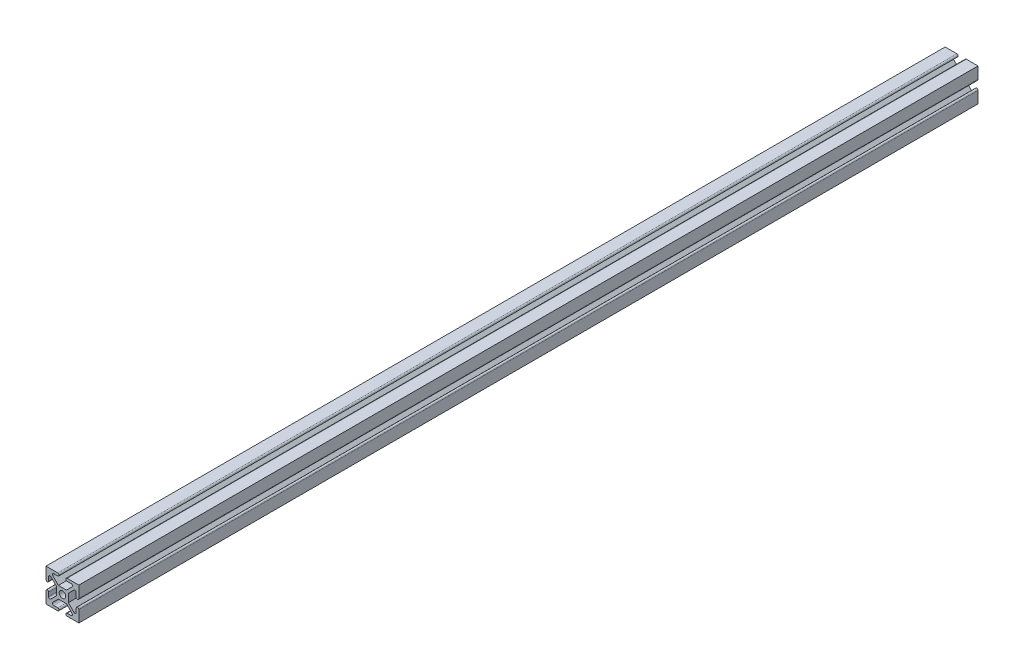
SolidWorks part; units mm, degrees
ref_plane "Front Plane" through (0, 0, 0) normal (0, 0, 1) x (1, 0, 0)
ref_plane "Top Plane" through (0, 0, 0) normal (0, 1, 0) x (1, 0, 0)
ref_plane "Right Plane" through (0, 0, 0) normal (1, 0, 0) x (0, 0, -1)
sketch "Sketch2" plane through (0, 0, 0) normal (0, 0, 1) x (1, 0, 0)
  line L0 (9.4142, 17) -> (5.1716, 21.2426)
  line L5 (9.4142, 17) -> (12.5, 17)
  line L9 (5.8995, 23) -> (8.8995, 23)
  line L10 (8.8995, 25) -> (0, 25)
  line L11 (0, 25) -> (8.8995, 25)
  line L12 (0, 16.1005) -> (0, 25)
  line L13 (2, 19.1005) -> (2, 16.1005)
  line L14 (8, 15.5858) -> (3.7574, 19.8284)
  line L15 (0, 25) -> (35355.3391, -35330.3391) construction
  line L16 (12.5, 12.5) -> (35367.8391, 35367.8391) construction
  line L17 (12.6363, 12.5) -> (50012.6363, 12.5) construction
  line L18 (12.5, 12.3637) -> (12.5, 50012.3637) construction
  line L19 (8, 15.5858) -> (8, 12.5)
  line L20 (9.4142, 8) -> (12.5, 8)
  line L21 (9.4142, 8) -> (5.1716, 3.7574)
  line L22 (5.8995, 2) -> (8.8995, 2)
  line L23 (8.8995, 0) -> (0, 0)
  line L24 (0, 8.8995) -> (0, 0)
  line L25 (2, 5.8995) -> (2, 8.8995)
  line L26 (8, 9.4142) -> (8, 12.5)
  line L27 (8, 9.4142) -> (3.7574, 5.1716)
  line L28 (15.5858, 17) -> (12.5, 17)
  line L29 (15.5858, 17) -> (19.8284, 21.2426)
  line L30 (19.1005, 23) -> (16.1005, 23)
  line L31 (16.1005, 25) -> (25, 25)
  line L32 (25, 16.1005) -> (25, 25)
  line L33 (23, 19.1005) -> (23, 16.1005)
  line L34 (17, 15.5858) -> (21.2426, 19.8284)
  line L35 (17, 15.5858) -> (17, 12.5)
  line L36 (17, 9.4142) -> (17, 12.5)
  line L37 (15.5858, 8) -> (12.5, 8)
  line L38 (17, 9.4142) -> (21.2426, 5.1716)
  line L39 (23, 5.8995) -> (23, 8.8995)
  line L40 (25, 8.8995) -> (25, 0)
  line L41 (16.1005, 0) -> (25, 0)
  line L42 (19.1005, 2) -> (16.1005, 2)
  line L43 (15.5858, 8) -> (19.8284, 3.7574)
  arc A0 (5.1716, 21.2426) -> (5.8995, 23) centre (5.8995, 21.9706) cw
  arc A1 (0, 16.1005) -> (2, 16.1005) centre (1, 16.1005) ccw
  arc A2 (8.8995, 25) -> (8.8995, 23) centre (8.8995, 24) cw
  arc A3 (3.7574, 19.8284) -> (2, 19.1005) centre (3.0294, 19.1005) ccw
  arc A4 (5.1716, 3.7574) -> (5.8995, 2) centre (5.8995, 3.0294) ccw
  arc A5 (8.8995, 0) -> (8.8995, 2) centre (8.8995, 1) ccw
  arc A6 (0, 8.8995) -> (2, 8.8995) centre (1, 8.8995) cw
  arc A7 (3.7574, 5.1716) -> (2, 5.8995) centre (3.0294, 5.8995) cw
  arc A8 (19.8284, 21.2426) -> (19.1005, 23) centre (19.1005, 21.9706) ccw
  arc A9 (16.1005, 25) -> (16.1005, 23) centre (16.1005, 24) ccw
  arc A10 (25, 16.1005) -> (23, 16.1005) centre (24, 16.1005) cw
  arc A11 (21.2426, 19.8284) -> (23, 19.1005) centre (21.9706, 19.1005) cw
  arc A12 (19.8284, 3.7574) -> (19.1005, 2) centre (19.1005, 3.0294) cw
  arc A13 (21.2426, 5.1716) -> (23, 5.8995) centre (21.9706, 5.8995) ccw
  arc A14 (25, 8.8995) -> (23, 8.8995) centre (24, 8.8995) ccw
  arc A15 (16.1005, 0) -> (16.1005, 2) centre (16.1005, 1) cw
  circle A16 centre (12.5, 12.5) radius 2.5
  dimension "D14" = 5
  dimension "D2" = 1.0294
  dimension "D3" = 12.5
  dimension "D4" = 12.5
  dimension "D5" = 17.6777
  dimension "D7" = 45
  dimension "D9" = 12.5
  dimension "D10" = 6
  dimension "D11" = 3
  dimension "D12" = 1
  dimension "D13" = 2
extrude "Boss-Extrude1" add sketch "Sketch2" along normal blind 200 contours A15 L41 L40 A14 L39 A13 L38 L36 L35 L34 A11 L33 A10 L32 L31 A9 L30 A8 L29 L28 L5 L0 A0 L9 A2 L10 L12 A1 L13 A3 L14 L19 L26 L27 A7 L25 A6 L24 L23 A5 L22 A4 L21 L20 L37 L43 A12 L42 A16 region at (10.9571, 16.6464, 0)
sketch "Croquis1" plane through (0, 0, 200) normal (0, 0, 1) x (1, 0, 0)
  line L0 (2, 8.8995) -> (2, 5.8995)
  line L1 (3.7574, 5.1716) -> (8, 9.4142)
  line L2 (8, 9.4142) -> (8, 15.5858)
  line L3 (5.8995, 23) -> (8.8995, 23)
  line L4 (0, 16.1005) -> (0, 25)
  line L5 (0, 25) -> (8.8995, 25)
  line L6 (2, 16.1005) -> (2, 19.1005)
  line L7 (8, 15.5858) -> (3.7574, 19.8284)
  line L8 (0, 8.8995) -> (0, 0)
  line L9 (0, 0) -> (8.8995, 0)
  line L10 (8.8995, 2) -> (5.8995, 2)
  line L11 (5.1716, 3.7574) -> (9.4142, 8)
  line L12 (9.4142, 8) -> (15.5858, 8)
  line L13 (15.5858, 8) -> (19.8284, 3.7574)
  line L14 (19.1005, 2) -> (16.1005, 2)
  line L15 (16.1005, 0) -> (25, 0)
  line L16 (25, 0) -> (25, 8.8995)
  line L17 (23, 5.8995) -> (23, 8.8995)
  line L18 (21.2426, 5.1716) -> (17, 9.4142)
  line L19 (17, 9.4142) -> (17, 15.5858)
  line L20 (17, 15.5858) -> (21.2426, 19.8284)
  line L21 (23, 19.1005) -> (23, 16.1005)
  line L22 (25, 16.1005) -> (25, 25)
  line L23 (25, 25) -> (16.1005, 25)
  line L24 (16.1005, 23) -> (19.1005, 23)
  line L25 (19.8284, 21.2426) -> (15.5858, 17)
  line L26 (15.5858, 17) -> (9.4142, 17)
  line L27 (9.4142, 17) -> (5.1716, 21.2426)
  circle A0 centre (1, 16.1005) radius 1
  circle A1 centre (1, 8.8995) radius 1
  circle A2 centre (8.8995, 1) radius 1
  circle A3 centre (16.1005, 1) radius 1
  circle A4 centre (24, 8.8995) radius 1
  circle A5 centre (8.8995, 24) radius 1
  circle A6 centre (16.1005, 24) radius 1
  circle A7 centre (24, 16.1005) radius 1
  circle A14 centre (3.0294, 19.1005) radius 1.0294
  circle A15 centre (3.0294, 5.8995) radius 1.0294
  circle A16 centre (5.8995, 3.0294) radius 1.03
  circle A17 centre (19.1005, 3.0294) radius 1.0294
  circle A18 centre (21.9706, 5.8995) radius 1.0294
  circle A19 centre (21.9706, 19.1005) radius 1.0294
  circle A20 centre (19.1005, 21.9706) radius 1.0294
  circle A21 centre (5.8995, 21.9706) radius 1.0294
  circle M2 centre (12.5, 12.5) radius 2.5
  arc M3 (16.1005, 2) -> (16.1005, 0) centre (16.1005, 1) ccw
  line M4 (16.1005, 0) -> (25, 0)
  line M5 (25, 0) -> (25, 8.8995)
  arc M6 (25, 8.8995) -> (23, 8.8995) centre (24, 8.8995) ccw
  line M7 (23, 8.8995) -> (23, 5.8995)
  arc M8 (23, 5.8995) -> (21.2426, 5.1716) centre (21.9706, 5.8995) cw
  line M9 (21.2426, 5.1716) -> (17, 9.4142)
  line M10 (17, 9.4142) -> (17, 15.5858)
  line M11 (17, 15.5858) -> (21.2426, 19.8284)
  arc M12 (21.2426, 19.8284) -> (23, 19.1005) centre (21.9706, 19.1005) cw
  line M13 (23, 19.1005) -> (23, 16.1005)
  arc M14 (23, 16.1005) -> (25, 16.1005) centre (24, 16.1005) ccw
  line M15 (25, 16.1005) -> (25, 25)
  line M16 (25, 25) -> (16.1005, 25)
  line M18 (16.1005, 23) -> (19.1005, 23)
  arc M19 (19.1005, 23) -> (19.8284, 21.2426) centre (19.1005, 21.9706) cw
  line M20 (19.8284, 21.2426) -> (15.5858, 17)
  line M21 (15.5858, 17) -> (9.4142, 17)
  line M22 (9.4142, 17) -> (5.1716, 21.2426)
  arc M23 (5.1716, 21.2426) -> (5.8995, 23) centre (5.8995, 21.9706) cw
  line M24 (5.8995, 23) -> (8.8995, 23)
  arc M25 (8.8995, 23) -> (8.8995, 25) centre (8.8995, 24) ccw
  line M26 (8.8995, 25) -> (0, 25)
  line M27 (0, 25) -> (0, 16.1005)
  arc M28 (0, 16.1005) -> (2, 16.1005) centre (1, 16.1005) ccw
  line M29 (2, 16.1005) -> (2, 19.1005)
  arc M30 (2, 19.1005) -> (3.7574, 19.8284) centre (3.0294, 19.1005) cw
  line M31 (3.7574, 19.8284) -> (8, 15.5858)
  line M32 (8, 15.5858) -> (8, 9.4142)
  line M33 (8, 9.4142) -> (3.7574, 5.1716)
  arc M34 (3.7574, 5.1716) -> (2, 5.8995) centre (3.0294, 5.8995) cw
  line M35 (2, 5.8995) -> (2, 8.8995)
  arc M36 (2, 8.8995) -> (0, 8.8995) centre (1, 8.8995) ccw
  line M37 (0, 8.8995) -> (0, 0)
  line M38 (0, 0) -> (8.8995, 0)
  arc M39 (8.8995, 0) -> (8.8995, 2) centre (8.8995, 1) ccw
  line M40 (8.8995, 2) -> (5.8995, 2)
  line M43 (9.4142, 8) -> (15.5858, 8)
  line M44 (15.5858, 8) -> (19.8284, 3.7574)
  arc M45 (19.8284, 3.7574) -> (19.1005, 2) centre (19.1005, 3.0294) cw
  line M46 (19.1005, 2) -> (16.1005, 2)
extrude "Saliente-Extruir1" add sketch "Croquis1" along normal blind 484 contours A16 L11 A3 A4 A7 A6 A5 A0 A1 A2 M43 M44 M45 M46 M4 M5 M7 M8 M9 M10 M11 M12 M13 M15 M16 M18 M19 M20 M21 M22 M23 M24 M26 M27 M29 M30 M31 M32 M33 M34 M35 M37 M38 M40 M2 | A5 M25 | A7 M14 | A0 M28 | A1 M36 | A2 M39 | A3 M3 | A4 M6 | A6 region at (1, 8.8995, 200) region at (1.6464, 7.3995, 200) region at (8.8995, 1, 200) region at (1, 16.1005, 200) region at (8.8995, 24, 200) region at (16.1005, 1, 200) region at (24, 8.8995, 200) region at (24, 16.1005, 200)
